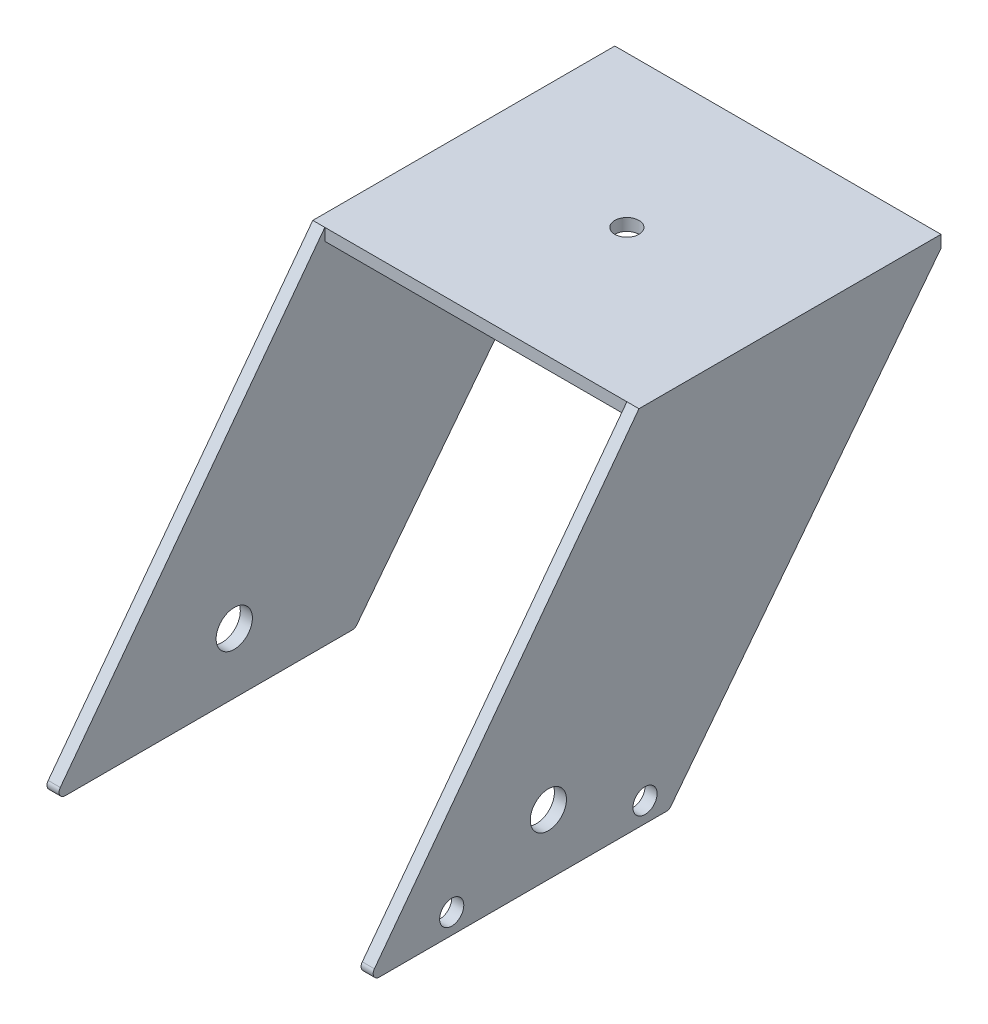
SolidWorks part; units mm, degrees
ref_plane "Front Plane" through (0, 0, 0) normal (0, 0, 1) x (1, 0, 0)
ref_plane "Top Plane" through (0, 0, 0) normal (0, 1, 0) x (1, 0, 0)
ref_plane "Right Plane" through (0, 0, 0) normal (1, 0, 0) x (0, 0, -1)
sketch "Sketch2" plane through (0, 0, 0) normal (0, 1, 0) x (1, 0, 0)
  line L1 (-25, 25) -> (25, 25)
  line L2 (-25, 25) -> (-25, -25)
  line L3 (-25, -25) -> (25, -25)
  line L4 (25, 25) -> (25, -25)
  circle A0 centre (0, 0) radius 2
  dimension "D5" = 4
  dimension "D1" = 50
  dimension "D2" = 50
  dimension "D3" = 25
  dimension "D4" = 25
extrude "Boss-Extrude1" add sketch "Sketch2" along normal blind 2
sketch "Sketch3" plane through (25, 0, 0) normal (1, 0, 0) x (0, 0, -1)
  line L0 (-25, 2) -> (-70, -58)
  line L1 (-70, -58) -> (-20, -58)
  line L2 (-20, -58) -> (25, 0)
  line L3 (-25, 2) -> (25, 2) construction
  line L4 (25, 0) -> (25, 2)
  line L5 (25, 2) -> (-25, 2)
  line L6 (-40, -48) -> (-31.1674, -48) construction
  circle A0 centre (-40, -48) radius 3
  circle A1 centre (-56, -54.68) radius 2
  circle A2 centre (-24, -54.683) radius 2
  dimension "D6" = 6
  dimension "D9" = 4
  dimension "D12" = 4
  dimension "D1" = 50
  dimension "D2" = 40
  dimension "D3" = 50
  dimension "D5" = 10
  dimension "D4" = 30
  dimension "D7" = 16
  dimension "D8" = 6.68
  dimension "D10" = 16
  dimension "D11" = 6.683
sketch "Sketch4" plane through (-25, 0, 0) normal (-1, 0, 0) x (0, 0, 1)
  line L0 (25, 2) -> (-25, 2)
  line L1 (-25, 2) -> (-25, 0) construction
  line L2 (-25, 2) -> (25, 2) construction
  line L3 (-25, 0.0263) -> (-25, 2)
  line L6 (-25, 2.0263) -> (-25, -47.9737) construction
  line L8 (20, -58) -> (-25, 0.0263)
  line L9 (70, -58) -> (20, -58)
  line L10 (25, 2) -> (70, -58)
  circle A1 centre (40, -48) radius 3
  circle A2 centre (40, -48) radius 3 construction
  dimension "D1" = 6
extrude "Boss-Extrude2" add sketch "Sketch4" along normal blind 2
extrude "Boss-Extrude3" add sketch "Sketch3" along normal blind 2
fillet "Fillet1" radius 1 2 edges at (26, -58, 20) (-26, -58, 20)
fillet "Fillet2" radius 1 2 edges at (26, -58, 70) (-26, -58, 70)
equation "\"d\"= 40"
equation "\"D2@Sketch3\"=\"d\""
